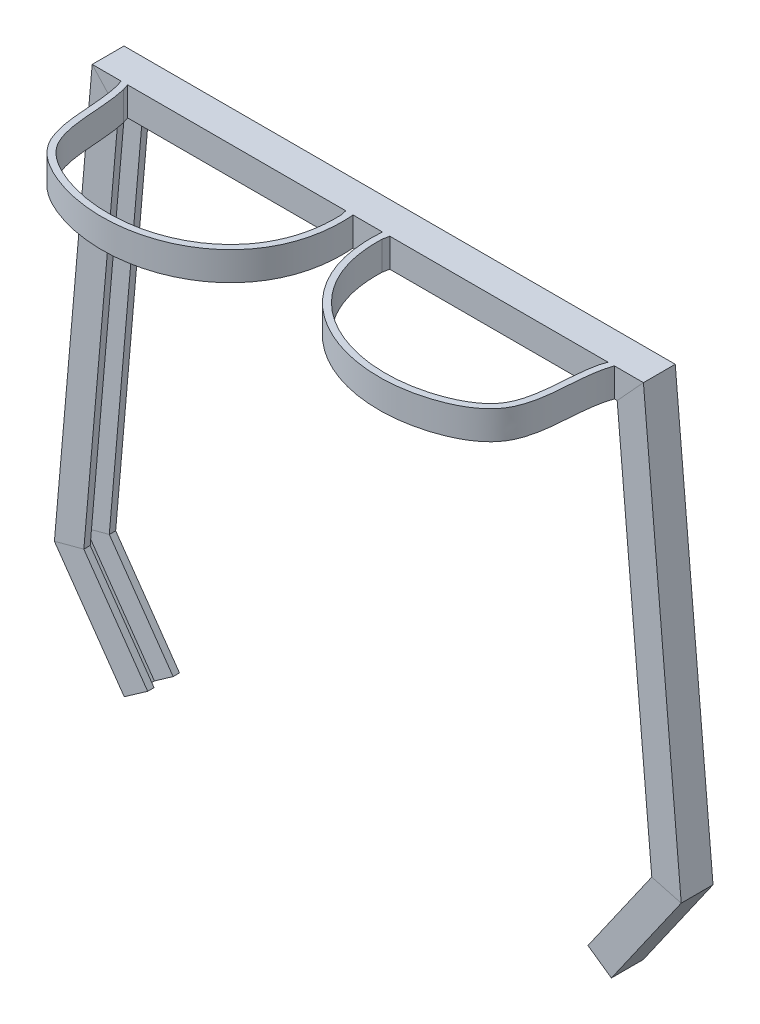
SolidWorks part; units mm, degrees
ref_plane "前视基准面" through (0, 0, 0) normal (0, 0, 1) x (1, 0, 0)
ref_plane "上视基准面" through (0, 0, 0) normal (0, 1, 0) x (1, 0, 0)
ref_plane "右视基准面" through (0, 0, 0) normal (1, 0, 0) x (0, 0, -1)
sketch "草图1" plane through (0, 0, 0) normal (0, 1, 0) x (1, 0, 0)
  line L0 (-85, 29.8187) -> (85, 29.8187)
  line L1 (85, 29.8187) -> (85, -30.1813)
  line L2 (85, -30.1813) -> (-85, -30.1813)
  line L3 (-85, -30.1813) -> (-85, 29.8187)
  line L4 (-77.5, 21.6616) -> (77.5, 21.6616)
  line L5 (-77.5, 21.6616) -> (-77.5, 11.6616)
  line L6 (-77.5, 11.6616) -> (-4.6224, 11.6616)
  line L8 (-74.8263, 9.6616) -> (-6.5113, 9.6616) construction
  line L10 (-4.6224, 11.6616) -> (4.6224, 11.6616)
  line L11 (0, 29.8187) -> (0, -30.1813) construction
  line L12 (77.5, 11.6616) -> (4.6224, 11.6616)
  line L13 (77.5, 21.6616) -> (77.5, 11.6616)
  spline S0 degree 3 poles (-77.5, 11.6616) (-74.4077, 3.1869) (-78.1308, -15.9273) (-40.2589, -37.426) (-2.1163, -20.689) (-4.6224, 11.6616) knots 0 0 0 0 0.246122 0.369792 1 1 1 1
  spline S1 degree 1 poles (-74.8263, 9.6616) (-6.5113, 9.6616) knots 0 0 1 1 construction
  spline S2 degree 3 poles (-74.8263, 9.6616) (-74.5371, 8.4402) (-74.1186, 5.9785) (-73.6218, 0.8691) (-73.2546, -5.557) (-72.241, -11.3706) (-70.6014, -15.2078) (-68.2701, -18.4305) (-63.7315, -21.7629) (-56.8543, -24.5334) (-49.7226, -26.1197) (-40.0582, -26.6566) (-30.6361, -24.878) (-22.3142, -20.9083) (-16.8289, -16.8747) (-12.2912, -11.8166) (-9.4499, -6.76) (-7.8343, -2.2025) (-6.9771, 1.4731) (-6.5812, 4.7599) (-6.4697, 7.5102) (-6.4856, 8.9503) (-6.5113, 9.6616) knots 0.022831 0.022831 0.022831 0.022831 0.052972 0.083113 0.143395 0.203676 0.233817 0.263958 0.324239 0.384521 0.444802 0.505084 0.625647 0.685929 0.74621 0.806492 0.866773 0.896914 0.927055 0.957196 0.972266 0.987337 0.987337 0.987337 0.987337
  spline S3 degree 1 poles (-74.8263, 9.6616) (-75.4985, 11.6616) knots 0 0 1 1
  spline S4 degree 1 poles (-6.5113, 9.6616) (-6.9074, 11.6616) knots 0 0 1 1
  spline S5 degree 1 poles (74.8263, 9.6616) (75.4985, 11.6616) knots 0 0 1 1
  spline S6 degree 1 poles (6.5113, 9.6616) (6.9074, 11.6616) knots 0 0 1 1
  spline S7 degree 3 poles (74.8263, 9.6616) (74.5371, 8.4402) (74.1186, 5.9785) (73.6218, 0.8691) (73.2546, -5.557) (72.241, -11.3706) (70.6014, -15.2078) (68.2701, -18.4305) (63.7315, -21.7629) (56.8543, -24.5334) (49.7226, -26.1197) (40.0582, -26.6566) (30.6361, -24.878) (22.3142, -20.9083) (16.8289, -16.8747) (12.2912, -11.8166) (9.4499, -6.76) (7.8343, -2.2025) (6.9771, 1.4731) (6.5812, 4.7599) (6.4697, 7.5102) (6.4856, 8.9503) (6.5113, 9.6616) knots 0.022831 0.022831 0.022831 0.022831 0.052972 0.083113 0.143395 0.203676 0.233817 0.263958 0.324239 0.384521 0.444802 0.505084 0.625647 0.685929 0.74621 0.806492 0.866773 0.896914 0.927055 0.957196 0.972266 0.987337 0.987337 0.987337 0.987337
  spline S8 degree 3 poles (77.5, 11.6616) (74.4077, 3.1869) (78.1308, -15.9273) (40.2589, -37.426) (2.1163, -20.689) (4.6224, 11.6616) knots 0 0 0 0 0.246122 0.369792 1 1 1 1
  point P3 (0, 29.8187)
  point P25 (0, 11.6616)
  point P31 (0, 21.6616)
  dimension "D1" = 60
  dimension "D2" = 170
  dimension "D3" = 10
  dimension "D4" = 77.5
  dimension "D5" = 2
extrude "frame_前端" add sketch "草图1" along normal blind 9 contours L13 L4 L5 L6 L10 L12 | S8 L12 S5 S7 S6 | S4 S2 S3 L6 S0 region at (0, 0, -16.6616) region at (-76.4992, 0, -10.8291) region at (42.3457, 0, 27.4934)
sketch "草图4" plane through (77.5, 0, 0) normal (1, 0, 0) x (0, 0, -1)
  line L0 (11.6616, 9) -> (11.6616, 0)
  line L2 (21.6616, 0) -> (21.6616, 9)
  line L3 (21.6616, 9) -> (11.6616, 9)
  line L4 (11.6616, 9) -> (21.6616, 0) construction
  line L5 (11.6616, 0) -> (21.6616, 9) construction
  line L6 (11.6616, 0) -> (13.6616, 0)
  line L7 (13.6616, 0) -> (13.6616, 7.2)
  line L8 (13.6616, 7.2) -> (19.6616, 7.2)
  line L9 (19.6616, 7.2) -> (19.6616, 0)
  line L10 (19.6616, 0) -> (21.6616, 0)
  line L11 (13.6616, 0) -> (19.6616, 0)
  line L12 (11.6616, 9) -> (11.6616, 0)
  line L13 (13.6616, 0) -> (13.6616, 7.2)
  line L14 (19.6616, 7.2) -> (19.6616, 0)
  line L15 (21.6616, 0) -> (21.6616, 9)
  point P4 (16.6616, 4.5)
  point P24 (16.6616, 4.5)
  dimension "D1" = 2
ref_plane "基准面2" through (0, 0, -16.6616) normal (0, 0, -1) x (-1, 0, 0)
sketch "草图5" plane through (0, 0, -16.6616) normal (0, 0, -1) x (-1, 0, 0)
  line L0 (-77.5, 4.5) -> (-82.5, 4.5)
  line L1 (-82.5, 4.5) -> (-93.8735, -125.5)
  line L2 (-93.8735, -125.5) -> (-72.8673, -155.5)
  dimension "D1" = 5
  dimension "D2" = 130
  dimension "D3" = 30
  dimension "D4" = 140
  dimension "D5" = 95
sweep "扫描1" add profiles "草图4" path "草图5"
ref_plane "基准面3" through (0, 0, -16.6616) normal (0, 0, -1) x (-1, 0, 0)
sketch "草图6" plane through (0, 0, -16.6616) normal (0, 0, -1) x (-1, 0, 0)
  line L0 (77.5, 4.5) -> (82.5, 4.5)
  line L1 (77.5, 9) -> (77.5, 0) construction
  line L2 (82.5, 4.5) -> (93.8735, -125.5)
  line L3 (93.8735, -125.5) -> (72.8673, -155.5)
  dimension "D1" = 5
  dimension "D2" = 95
  dimension "D3" = 140
  dimension "D4" = 30
  dimension "D5" = 130
sketch "草图7" plane through (-77.5, 0, 0) normal (-1, 0, 0) x (0, 0, 1)
  line L0 (-21.6616, 9) -> (-21.6616, 0)
  line L1 (-21.6616, 0) -> (-19.6616, 0)
  line L2 (-19.6616, 0) -> (-19.6616, 7.2)
  line L3 (-19.6616, 7.2) -> (-13.6616, 7.2)
  line L4 (-13.6616, 7.2) -> (-13.6616, 0)
  line L5 (-13.6616, 0) -> (-11.6616, 0)
  line L6 (-11.6616, 0) -> (-11.6616, 9)
  line L7 (-11.6616, 9) -> (-21.6616, 9)
sweep "扫描2" add profiles "草图7" path "草图6"
ref_plane "基准面4" through (0, 0, 0) normal (1, 0, 0) x (0, 0, -1)
sketch "草图8" plane through (0, 0, 0) normal (1, 0, 0) x (0, 0, -1)
  line L0 (13.6616, 0) -> (19.6616, 0)
  line L1 (19.6616, 0) -> (19.6616, 7.2)
  line L2 (19.6616, 7.2) -> (13.6616, 7.2)
  line L3 (13.6616, 7.2) -> (13.6616, 0)
  line L4 (21.6616, 9) -> (21.6616, -126.7394) construction
  line L5 (11.6616, 9) -> (11.6616, 0) construction
  dimension "D1" = 7.2
  dimension "D2" = 2
  dimension "D3" = 2
extrude "切除-拉伸1" cut sketch "草图8" against normal blind 77.5 and the other way blind 77.5
